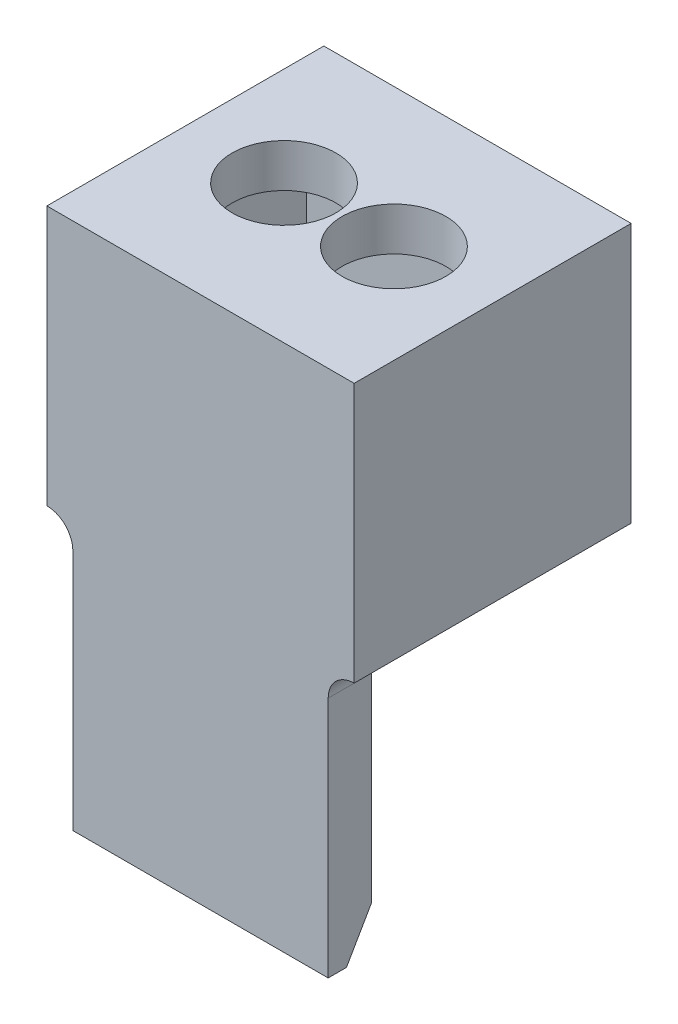
SolidWorks part; units mm, degrees
ref_plane "Front Plane" through (0, 0, 0) normal (0, 0, 1) x (1, 0, 0)
ref_plane "Top Plane" through (0, 0, 0) normal (0, 1, 0) x (1, 0, 0)
ref_plane "Right Plane" through (0, 0, 0) normal (1, 0, 0) x (0, 0, -1)
sketch "Sketch1" plane through (0, 0, 2.8596) normal (0, 0, 1) x (1, 0, 0)
  line L1 (8.4252, 9.9223) -> (11.3752, 9.9223)
  line L2 (8.4252, 9.9223) -> (8.4252, 15.5223)
  line L3 (8.4252, 15.5223) -> (11.3752, 15.5223)
  line L4 (11.3752, 9.9223) -> (11.3752, 15.5223)
  dimension "D1" = 5.6
extrude "Boss-Extrude1" add sketch "Sketch1" along normal blind 0.5
sketch "Sketch2" plane through (11.3752, 0, 0) normal (1, 0, 0) x (0, 0, -1)
  line L0 (-0.6596, 15.5223) -> (-0.6596, 11.4223) construction
  line L1 (-3.3596, 15.5223) -> (-0.1596, 15.5223)
  line L2 (-3.3596, 15.5223) -> (-3.3596, 13.0223)
  line L3 (-3.3596, 13.0223) -> (-0.1596, 13.0223)
  line L4 (-0.1596, 15.5223) -> (-0.1596, 13.0223)
  dimension "D1" = 2.5
  dimension "D2" = 0.5
extrude "Boss-Extrude2" add sketch "Sketch2" along normal blind 0.3
sketch "Sketch3" plane through (11.3752, 0, 0) normal (-1, 0, 0) x (0, 0, 1)
  line L0 (0.1596, 15.5223) -> (2.8596, 15.5223) construction
  line L1 (0.1596, 13.0223) -> (0.6596, 13.0223)
  line L2 (0.1596, 13.0223) -> (0.1596, 15.5223)
  line L3 (0.1596, 15.5223) -> (0.6596, 15.5223)
  line L4 (0.6596, 13.0223) -> (0.6596, 15.5223)
  line L5 (0.6596, 11.4223) -> (0.6596, 15.5223) construction
extrude "Boss-Extrude3" add sketch "Sketch3" along normal up to vertex (1.475 mm away)
sketch "Sketch4" plane through (0, 15.5223, 0) normal (0, 1, 0) x (1, 0, 0)
  line L1 (9.9002, -0.1596) -> (11.6752, -0.1596)
  line L2 (9.9002, -0.1596) -> (9.9002, -3.3596)
  line L3 (9.9002, -3.3596) -> (11.6752, -3.3596)
  line L4 (11.6752, -0.1596) -> (11.6752, -3.3596)
  circle A0 centre (10.5352, -1.7596) radius 0.6
  dimension "D1" = 1.2
extrude "Boss-Extrude4" add sketch "Sketch4" along normal blind 0.5 contours A0
mirror "Mirror1" about plane through (9.9002, 0, 0) normal (1, 0, 0) of "Boss-Extrude4", "Boss-Extrude3", "Boss-Extrude2"
chamfer "Chamfer1" distance 0.5 angle 30 1 edges at (9.9002, 9.9223, 2.8596)
fillet "Fillet1" radius 0.3 2 edges at (11.3752, 13.0223, 3.1096) (8.4252, 13.0223, 3.1096)
